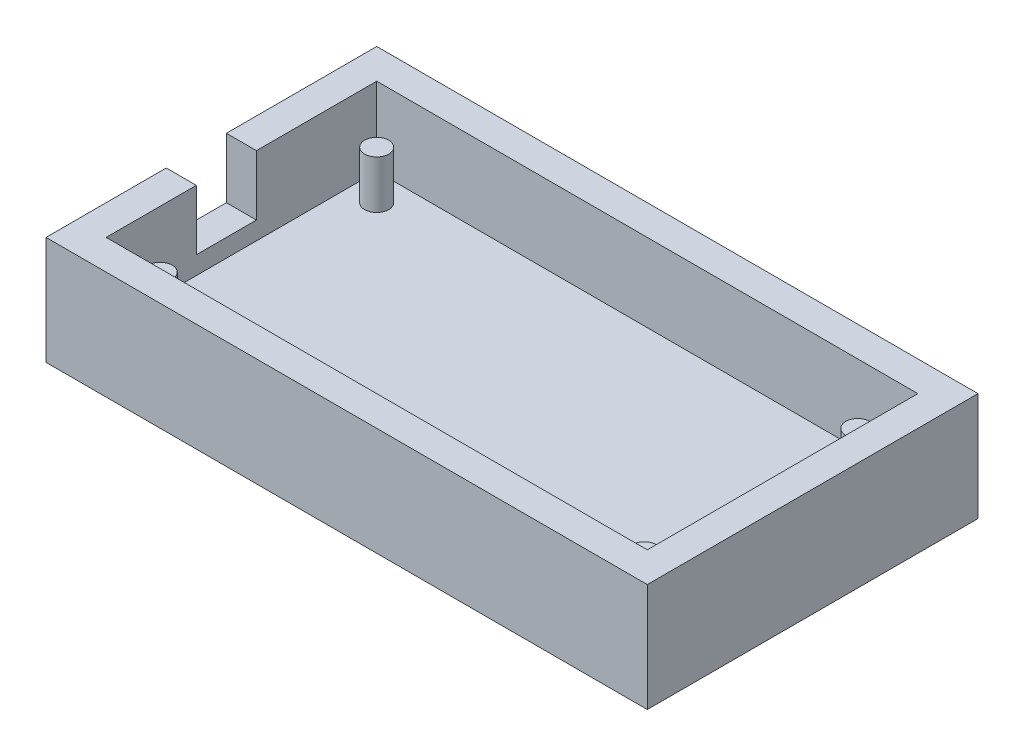
SolidWorks part; units mm, degrees
ref_plane "Front Plane" through (0, 0, 0) normal (0, 0, 1) x (1, 0, 0)
ref_plane "Top Plane" through (0, 0, 0) normal (0, 1, 0) x (1, 0, 0)
ref_plane "Right Plane" through (0, 0, 0) normal (1, 0, 0) x (0, 0, -1)
sketch "Sketch1" plane through (0, 0, 0) normal (0, 1, 0) x (1, 0, 0)
  line L1 (-18.458, 42.307) -> (81.542, 42.307)
  line L2 (-18.458, 42.307) -> (-18.458, -12.693)
  line L3 (-18.458, -12.693) -> (81.542, -12.693)
  line L4 (81.542, 42.307) -> (81.542, -12.693)
  dimension "D1" = 100
  dimension "D2" = 55
extrude "Boss-Extrude4" add sketch "Sketch1" against normal blind 5
sketch "Sketch2" plane through (0, 0, 0) normal (0, 1, 0) x (1, 0, 0)
  line L4 (-18.458, 42.307) -> (81.542, 42.307)
  line L5 (-18.458, 42.307) -> (-18.458, -12.693)
  line L6 (-18.458, -12.693) -> (81.542, -12.693)
  line L7 (81.542, 42.307) -> (81.542, -12.693)
  line L8 (76.542, -7.693) -> (-13.458, -7.693)
  line L9 (76.542, -7.693) -> (76.542, 37.307)
  line L10 (76.542, 37.307) -> (-13.458, 37.307)
  line L11 (-13.458, -7.693) -> (-13.458, 37.307)
  line L12 (-18.458, 17.307) -> (-13.458, 17.307)
  line L13 (-18.458, 17.307) -> (-18.458, 7.307)
  line L14 (-18.458, 7.307) -> (-13.458, 7.307)
  line L15 (-13.458, 17.307) -> (-13.458, 7.307)
  line M11 (-18.458, 42.307) -> (-18.458, -12.693)
  line M12 (-18.458, -12.693) -> (81.542, -12.693)
  line M13 (81.542, -12.693) -> (81.542, 42.307)
  line M14 (81.542, 42.307) -> (-18.458, 42.307)
  dimension "D1" = 15
  dimension "D5" = 90
  dimension "D2" = 20
  dimension "D6" = 45
  dimension "D7" = 5
  dimension "D8" = 5
extrude "Boss-Extrude6" add sketch "Sketch2" along normal blind 13 contours L14 L12 L11 L10 L9 L8 M11 M12 M13 M14 region at (31.542, 0, -41.1657)
extrude "Boss-Extrude7" add sketch "Sketch2<3>" along normal blind 3 contours L5 L14 L11 L12 region at (-15.958, 0, -12.307)
sketch "Sketch2<3>" plane through (0, 0, 0) normal (0, 1, 0) x (1, 0, 0) same geometry as "Sketch2"
sketch "Sketch4" plane through (0, 0, 0) normal (0, 1, 0) x (1, 0, 0)
  line L0 (-13.458, -7.693) -> (-13.458, 37.307) construction
  line L1 (76.542, 37.307) -> (-13.458, 37.307) construction
  line L2 (-13.458, -7.693) -> (-13.458, 7.307) construction
  line L3 (76.542, -7.693) -> (-13.458, -7.693) construction
  line L4 (76.542, -7.693) -> (76.542, 37.307) construction
  line L5 (76.542, -7.693) -> (-13.458, -7.693) construction
  circle A0 centre (-8.958, 32.807) radius 2
  circle A1 centre (-8.958, -3.193) radius 2
  circle A2 centre (71.542, -3.193) radius 2
  circle A3 centre (71.542, 32.307) radius 2
  dimension "D1" = 4.5
  dimension "D3" = 4.5
  dimension "D5" = 5
  dimension "D7" = 5
  dimension "D2" = 4.5
  dimension "D4" = 4.5
  dimension "D6" = 4.5
  dimension "D8" = 5
extrude "Boss-Extrude8" add sketch "Sketch4" along normal blind 8
